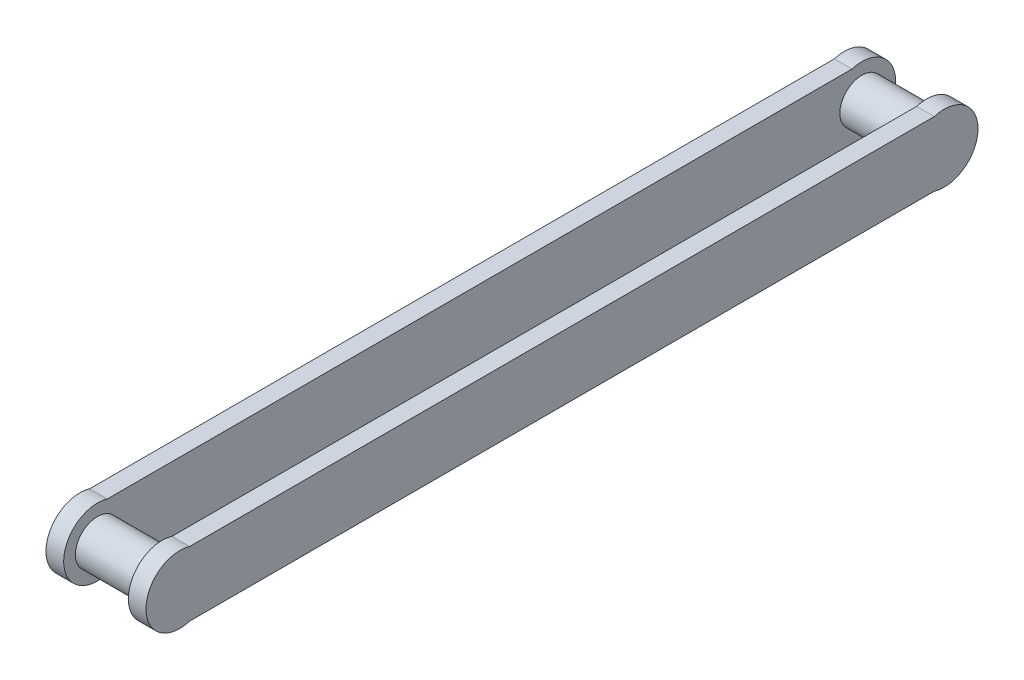
SolidWorks part; units mm, degrees
ref_plane "Front Plane" through (0, 0, 0) normal (0, 0, 1) x (1, 0, 0)
ref_plane "Top Plane" through (0, 0, 0) normal (0, 1, 0) x (1, 0, 0)
ref_plane "Right Plane" through (0, 0, 0) normal (1, 0, 0) x (0, 0, -1)
sketch "Sketch1" plane through (0, 0, 0) normal (1, 0, 0) x (0, 0, -1)
  line L0 (-89.172, -2.2228) -> (40.828, -2.2228) construction
  line L1 (-89.172, 3.2772) -> (40.828, 3.2772)
  line L2 (-89.172, 3.2772) -> (-89.172, -7.7228)
  line L3 (-89.172, -7.7228) -> (40.828, -7.7228)
  line L4 (40.828, 3.2772) -> (40.828, -7.7228)
  circle A0 centre (-89.172, -2.2228) radius 3.75
  circle A1 centre (-89.172, -2.2228) radius 5.75
  circle A2 centre (40.828, -2.2228) radius 3.75
  circle A3 centre (40.828, -2.2228) radius 5.75
  dimension "D1" = 7.5
  dimension "D2" = 2
  dimension "D3" = 130
  dimension "D4" = 11
extrude "Boss-Extrude1" add sketch "Sketch1" along normal blind 5.5 contours L2 A0 | L4 A2 | A2 L0 L4 | L0 A2 L4 | L0 L2 A0 | L2 L0 A0 region at (0, -0.6313, 87.5804) region at (0, -2.2228, 90.7635) region at (0, -3.8144, 87.5804) region at (0, -0.6313, -39.2365) region at (0, -3.8144, -39.2365) region at (0, -2.2228, -42.4196)
extrude "Boss-Extrude3" add sketch "Sketch1<4>" against normal blind 3 contours L0 A1 L3 A3 | A1 L0 A3 L1 | A0 L0 A1 L1 L2 | L0 A0 L2 L3 A1 | L2 A0 | L0 L2 A0 | L2 L0 A0 | L1 A1 L3 L2 A0 | L4 A2 | L0 A2 L4 | A2 L0 L4 | A3 L0 A2 L4 L1 | L3 A3 L1 L4 A2 | L0 A3 L3 L4 A2 region at (0, -0.6313, 87.5804) region at (0, -2.2228, 90.7635) region at (0, -3.8144, 87.5804) region at (0, 0.7972, 86.0566) region at (0, -5.2429, 86.0566) region at (0, -2.2228, 93.0589) region at (0, 0.5538, 24.172) region at (0, -4.9995, 24.172) region at (0, 0.7972, -37.7127) region at (0, -5.2429, -37.7127) region at (0, -0.6313, -39.2365) region at (0, -3.8144, -39.2365) region at (0, 2.288, -44.1685) region at (0, -2.2228, -42.4196)
sketch "Sketch1<4>" plane through (0, 0, 0) normal (1, 0, 0) x (0, 0, -1) same geometry as "Sketch1"
ref_plane "Plane1" through (5.5, 0, 0) normal (1, 0, 0) x (0, 0, -1)
mirror "Mirror1" about plane through (5.5, 0, 0) normal (1, 0, 0) of "Boss-Extrude3", "Boss-Extrude1"
